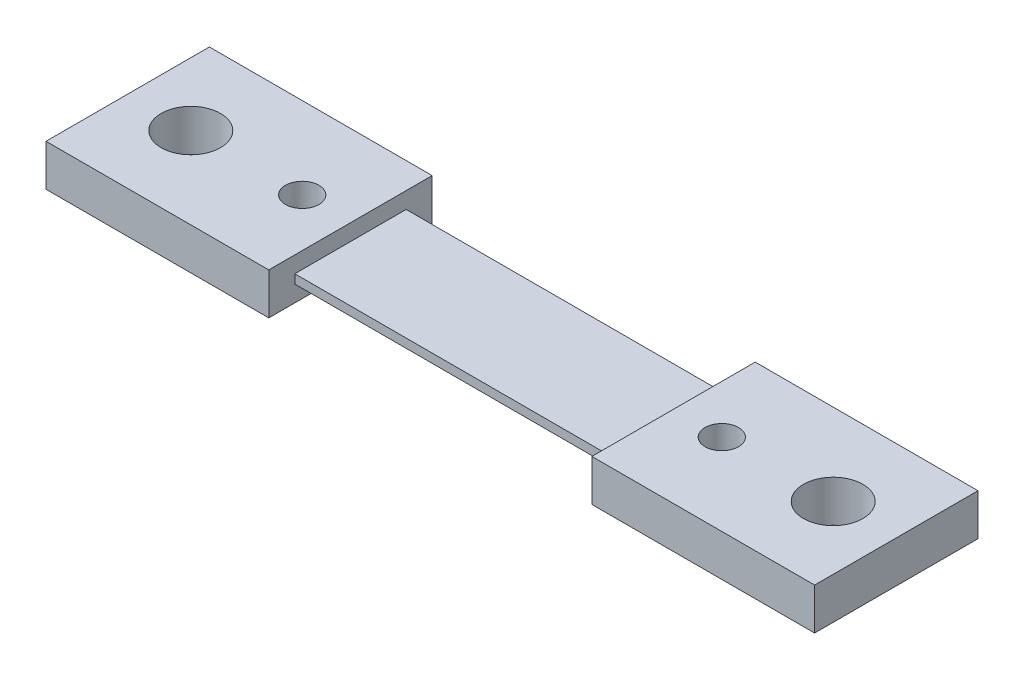
SolidWorks part; units mm, degrees
ref_plane "Front Plane" through (0, 0, 0) normal (0, 0, 1) x (1, 0, 0)
ref_plane "Top Plane" through (0, 0, 0) normal (0, 1, 0) x (1, 0, 0)
ref_plane "Right Plane" through (0, 0, 0) normal (1, 0, 0) x (0, 0, -1)
sketch "Sketch2" plane through (0, 0, 0) normal (0, 1, 0) x (1, 0, 0)
  line L1 (-21.75, 7.5) -> (21.75, 7.5)
  line L2 (-21.75, 7.5) -> (-21.75, -7.5)
  line L3 (-21.75, -7.5) -> (21.75, -7.5)
  line L4 (21.75, 7.5) -> (21.75, -7.5)
  line L5 (-21.75, 7.5) -> (21.75, -7.5) construction
  line L6 (-21.75, -7.5) -> (21.75, 7.5) construction
  point P0 (0, 0)
  dimension "D1" = 15
  dimension "D2" = 43.5
extrude "Boss-Extrude1" add sketch "Sketch2" along normal blind 0.6 and the other way blind 0.6
sketch "Sketch3" plane through (0, 0, 0) normal (0, 1, 0) x (1, 0, 0)
  line L0 (-36.75, 0) -> (0, 0) construction
  line L1 (51.75, -11) -> (21.75, -11)
  line L2 (51.75, -11) -> (51.75, 11)
  line L3 (51.75, 11) -> (21.75, 11)
  line L4 (21.75, -11) -> (21.75, 11)
  line L5 (51.75, -11) -> (21.75, 11) construction
  line L6 (51.75, 11) -> (21.75, -11) construction
  line L7 (-51.75, 11) -> (-21.75, 11)
  line L8 (-51.75, 11) -> (-51.75, -11)
  line L9 (-51.75, -11) -> (-21.75, -11)
  line L10 (-21.75, 11) -> (-21.75, -11)
  line L11 (-51.75, 11) -> (-21.75, -11) construction
  line L12 (-51.75, -11) -> (-21.75, 11) construction
  line L13 (0, 0) -> (36.75, 0) construction
  line L14 (-21.75, 7.5) -> (-21.75, -7.5) construction
  line L15 (21.75, -7.5) -> (21.75, 7.5) construction
  point P0 (36.75, 0)
  point P5 (-36.75, 0)
  dimension "D1" = 30
  dimension "D2" = 22
extrude "Boss-Extrude2" add sketch "Sketch3" along normal blind 2.8 and the other way blind 2.8
sketch "Sketch4" plane through (0, 0, 0) normal (0, 1, 0) x (1, 0, 0)
  line L0 (0, 0) -> (28.25, 0) construction
  line L1 (28.25, 0) -> (43.25, 0) construction
  line L2 (51.75, -11) -> (51.75, 11) construction
  line L3 (21.75, 11) -> (21.75, -11) construction
  line L4 (0, 0) -> (0, -7.5) construction
  line L5 (-21.75, -7.5) -> (21.75, -7.5) construction
  circle A0 centre (28.25, 0) radius 2.25
  circle A1 centre (43.25, 0) radius 4
  circle A2 centre (-43.25, 0) radius 4
  circle A3 centre (-28.25, 0) radius 2.25
  dimension "D1" = 4.5
  dimension "D2" = 8
  dimension "D3" = 8.5
  dimension "D4" = 6.5
extrude "Cut-Extrude1" cut sketch "Sketch4" against normal through all both and the other way through all
